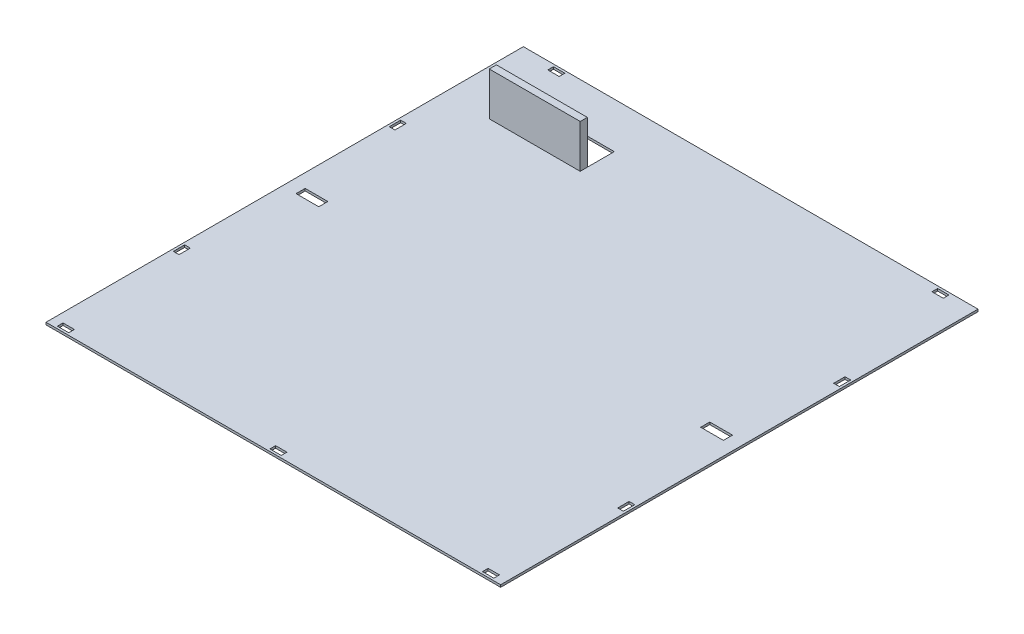
SolidWorks part; units mm, degrees
material "ABS"
ref_plane "Front Plane" through (0, 0, 0) normal (0, 0, 1) x (1, 0, 0)
ref_plane "Top Plane" through (0, 0, 0) normal (0, 1, 0) x (1, 0, 0)
ref_plane "Right Plane" through (0, 0, 0) normal (1, 0, 0) x (0, 0, -1)
sketch "Sketch1" plane through (0, 0, 0) normal (0, 1, 0) x (1, 0, 0)
  line L0 (-80, 73.1246) -> (-40, 73.1246)
  line L1 (100, 105) -> (-100, 105)
  line L2 (100, 105) -> (100, -105)
  line L3 (100, -105) -> (-100, -105)
  line L4 (-100, 105) -> (-100, -105)
  line L5 (100, 105) -> (-100, -105) construction
  line L6 (100, -105) -> (-100, 105) construction
  line L11 (94, 3) -> (84, 3)
  line L12 (94, 3) -> (94, -1)
  line L13 (94, -1) -> (84, -1)
  line L14 (84, 3) -> (84, -1)
  line L15 (94, 3) -> (84, -1) construction
  line L16 (94, -1) -> (84, 3) construction
  line L17 (-94, -1) -> (-84, -1)
  line L18 (-94, -1) -> (-94, 3)
  line L19 (-94, 3) -> (-84, 3)
  line L20 (-84, -1) -> (-84, 3)
  line L21 (-94, -1) -> (-84, 3) construction
  line L22 (-94, 3) -> (-84, -1) construction
  line L27 (-80, 70) -> (-40, 70)
  line L28 (-80, 70) -> (-80, 85)
  line L33 (-80, 85) -> (-40, 85)
  line L34 (-40, 70) -> (-40, 85)
  line L35 (96, -104) -> (91, -104)
  line L36 (96, -104) -> (96, -101.5)
  line L37 (96, -101.5) -> (91, -101.5)
  line L38 (91, -104) -> (91, -101.5)
  line L39 (96, -104) -> (91, -101.5) construction
  line L40 (96, -101.5) -> (91, -104) construction
  line L41 (-2.5, -104) -> (2.5, -104)
  line L42 (-2.5, -104) -> (-2.5, -101.5)
  line L43 (-2.5, -101.5) -> (2.5, -101.5)
  line L44 (2.5, -104) -> (2.5, -101.5)
  line L45 (-2.5, -104) -> (2.5, -101.5) construction
  line L46 (-2.5, -101.5) -> (2.5, -104) construction
  line L47 (-96, -104) -> (-91, -104)
  line L48 (-96, -104) -> (-96, -101.5)
  line L49 (-96, -101.5) -> (-91, -101.5)
  line L50 (-91, -104) -> (-91, -101.5)
  line L51 (-96, -104) -> (-91, -101.5) construction
  line L52 (-96, -101.5) -> (-91, -104) construction
  line L53 (-80.75, 104) -> (-85.75, 104)
  line L54 (-80.75, 104) -> (-80.75, 101.5)
  line L55 (-80.75, 101.5) -> (-85.75, 101.5)
  line L56 (-85.75, 104) -> (-85.75, 101.5)
  line L57 (-80.75, 104) -> (-85.75, 101.5) construction
  line L58 (-80.75, 101.5) -> (-85.75, 104) construction
  line L59 (83.25, 101.5) -> (88.25, 101.5)
  line L60 (83.25, 101.5) -> (83.25, 104)
  line L61 (83.25, 104) -> (88.25, 104)
  line L62 (88.25, 101.5) -> (88.25, 104)
  line L63 (83.25, 101.5) -> (88.25, 104) construction
  line L64 (83.25, 104) -> (88.25, 101.5) construction
  line L65 (99, -45) -> (96.5, -45)
  line L66 (99, -45) -> (99, -50)
  line L67 (99, -50) -> (96.5, -50)
  line L68 (96.5, -45) -> (96.5, -50)
  line L69 (99, -45) -> (96.5, -50) construction
  line L70 (99, -50) -> (96.5, -45) construction
  line L71 (99, 50) -> (96.5, 50)
  line L72 (99, 50) -> (99, 45)
  line L73 (99, 45) -> (96.5, 45)
  line L74 (96.5, 50) -> (96.5, 45)
  line L75 (99, 50) -> (96.5, 45) construction
  line L76 (99, 45) -> (96.5, 50) construction
  line L77 (-99, -45) -> (-96.5, -45)
  line L78 (-99, -45) -> (-99, -50)
  line L79 (-99, -50) -> (-96.5, -50)
  line L80 (-96.5, -45) -> (-96.5, -50)
  line L81 (-99, -45) -> (-96.5, -50) construction
  line L82 (-99, -50) -> (-96.5, -45) construction
  line L83 (-99, 45) -> (-96.5, 45)
  line L84 (-99, 45) -> (-99, 50)
  line L85 (-99, 50) -> (-96.5, 50)
  line L86 (-96.5, 45) -> (-96.5, 50)
  line L87 (-99, 45) -> (-96.5, 50) construction
  line L88 (-99, 50) -> (-96.5, 45) construction
  line L89 (-80, 70) -> (-40, 85) construction
  line L90 (-80, 85) -> (-40, 70) construction
  point P0 (0, 0)
  point P6 (89, 1)
  point P11 (-60, 77.5)
  point P23 (-89, 1)
  point P38 (93.5, -102.75)
  point P43 (0, -102.75)
  point P48 (-93.5, -102.75)
  point P53 (-83.25, 102.75)
  point P58 (85.75, 102.75)
  point P59 (97.75, -47.5)
  point P68 (97.75, -45)
  point P69 (97.75, 47.5)
  point P74 (-97.75, -47.5)
  point P79 (-97.75, 47.5)
  dimension "D7" = 20
  dimension "D8" = 20
  dimension "D9" = 15
  dimension "D17" = 10
  dimension "D1" = 200
  dimension "D2" = 210
  dimension "D6" = 104
  dimension "D10" = 40
  dimension "D16" = 6
  dimension "D18" = 4
  dimension "D19" = 104
  dimension "D20" = 6
  dimension "D21" = 4
  dimension "D22" = 10
  dimension "D31" = 4
  dimension "D32" = 1
  dimension "D33" = 5
  dimension "D34" = 2.5
  dimension "D35" = 1
  dimension "D36" = 100
  dimension "D37" = 5
  dimension "D38" = 2.5
  dimension "D39" = 1
  dimension "D40" = 4
  dimension "D41" = 5
  dimension "D42" = 2.5
  dimension "D43" = 14.25
  dimension "D44" = 1
  dimension "D45" = 5
  dimension "D46" = 2.5
  dimension "D47" = 14.25
  dimension "D48" = 1
  dimension "D49" = 5
  dimension "D50" = 2.5
  dimension "D51" = 1
  dimension "D52" = 5
  dimension "D53" = 2.5
  dimension "D54" = 55
  dimension "D55" = 55
  dimension "D56" = 1
  dimension "D57" = 5
  dimension "D58" = 2.5
  dimension "D59" = 1
  dimension "D60" = 55
  dimension "D61" = 2.5
  dimension "D62" = 5
  dimension "D63" = 55
  dimension "D64" = 1
  dimension "D65" = 2.5
  dimension "D66" = 5
extrude "MainBody" add sketch "Sketch1" along normal blind 1 contours L1 L4 L3 L2 L86 L83 L84 L85 L74 L71 L72 L73 L68 L65 L66 L67 L62 L59 L60 L61 L56 L53 L54 L55 L50 L47 L48 L49 L44 L41 L42 L43 L20 L17 L18 L19 L14 L11 L12 L13 L35 region at (0.8729, 0, 1.0992)
extrude "Boss-Extrude1" add sketch "Sketch1<8>" along normal blind 20 contours L27 L34 L0 L28 region at (-60, 0, -71.5623)
sketch "Sketch1<8>" plane through (0, 0, 0) normal (0, 1, 0) x (1, 0, 0) same geometry as "Sketch1"
